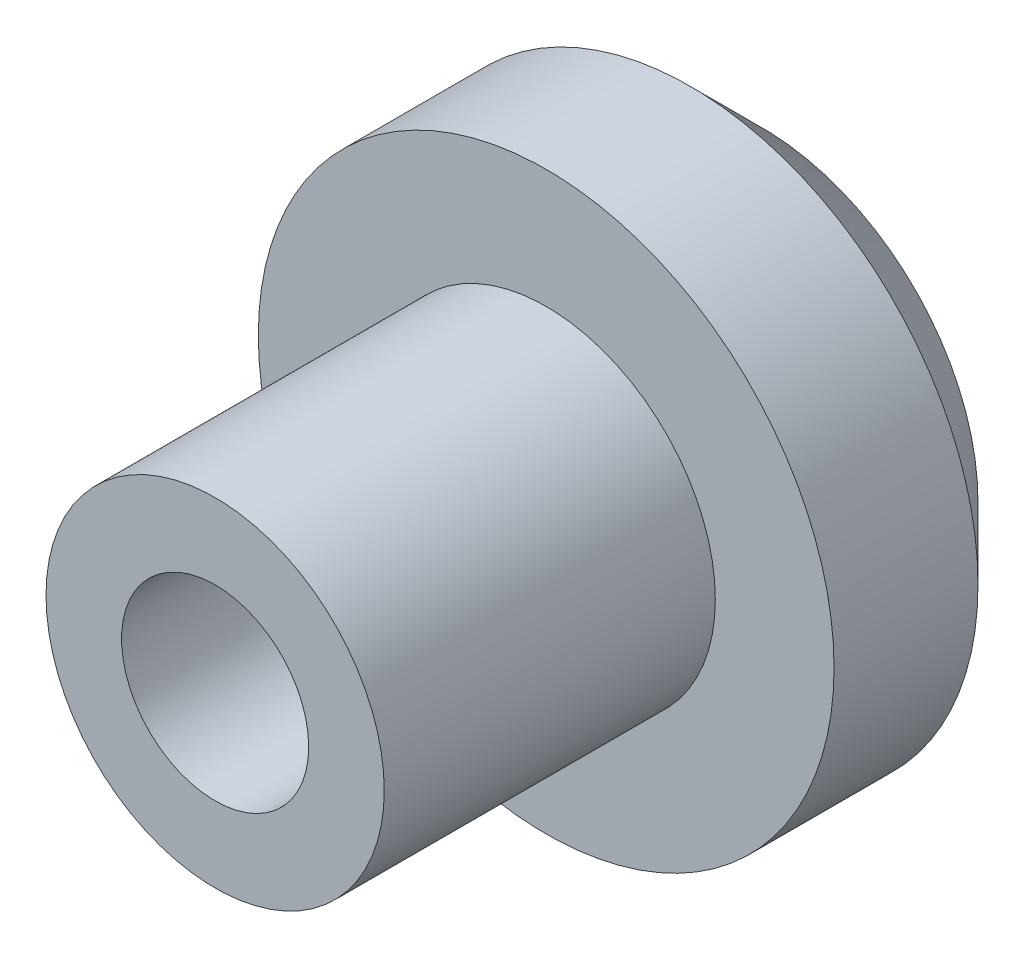
SolidWorks part; units mm, degrees
material "Copper"
ref_plane "Front Plane" through (0, 0, 0) normal (0, 0, 1) x (1, 0, 0)
ref_plane "Top Plane" through (0, 0, 0) normal (0, 1, 0) x (1, 0, 0)
ref_plane "Right Plane" through (0, 0, 0) normal (1, 0, 0) x (0, 0, -1)
sketch "Sketch1" plane through (0, 0, 0) normal (0, 0, 1) x (1, 0, 0)
  circle A0 centre (0, 0) radius 4
  dimension "D1" = 8
extrude "Boss-Extrude1" add sketch "Sketch1" along normal blind 3
sketch "Sketch2" plane through (0, 0, 3) normal (0, 0, 1) x (1, 0, 0)
  circle A0 centre (0, 0) radius 2.35
  dimension "D1" = 4.7
extrude "Boss-Extrude2" add sketch "Sketch2" along normal blind 4.6
sketch "Sketch3" plane through (0, 0, 7.6) normal (0, 0, 1) x (1, 0, 0)
  circle A0 centre (0, 0) radius 1.3
  dimension "D1" = 2.6
extrude "Cut-Extrude1" cut sketch "Sketch3" against normal through all
chamfer "Chamfer1" distance 1 angle 45 1 edges at (4, 0, 0)
